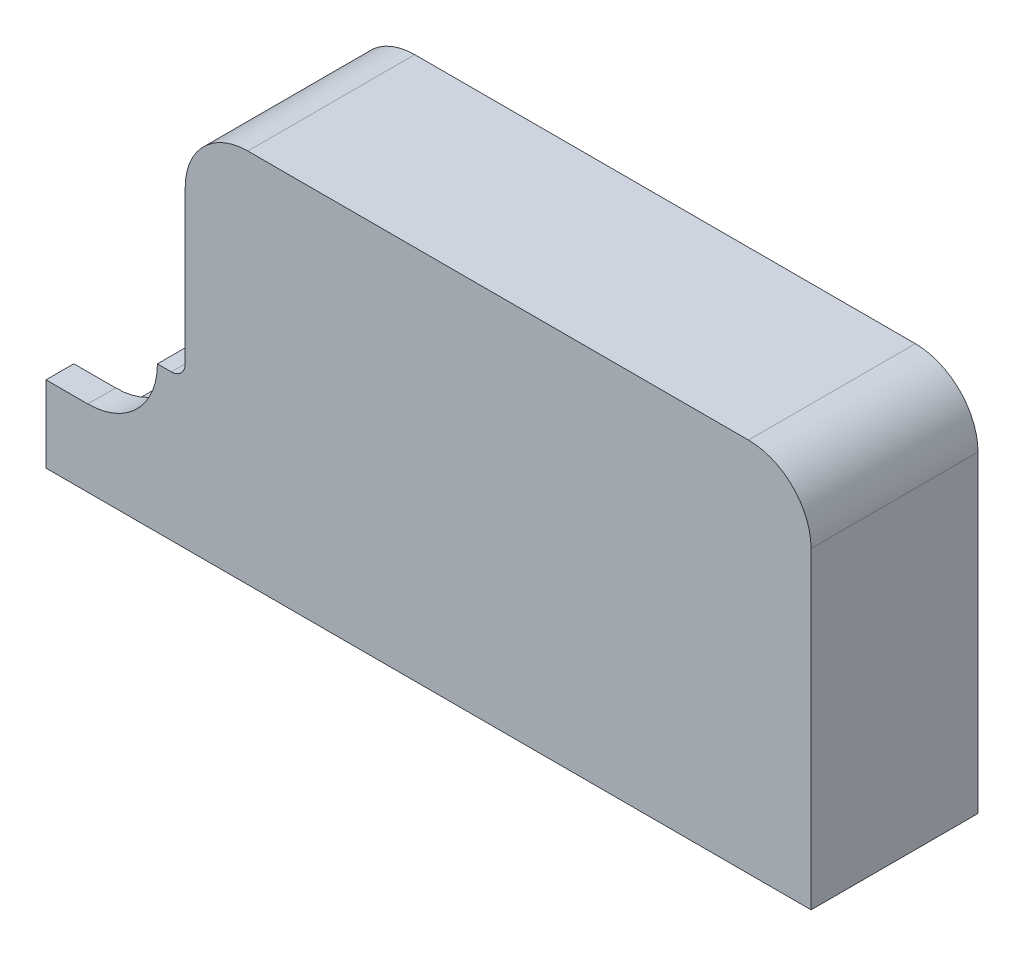
SolidWorks part; units mm, degrees
ref_plane "Front Plane" through (0, 0, 0) normal (0, 0, 1) x (1, 0, 0)
ref_plane "Top Plane" through (0, 0, 0) normal (0, 1, 0) x (1, 0, 0)
ref_plane "Right Plane" through (0, 0, 0) normal (1, 0, 0) x (0, 0, -1)
sketch "Sketch1" plane through (0, 0, 0) normal (0, 0, 1) x (1, 0, 0)
  line L30 (11.5095, 13.5276) -> (11.5095, 22.5276)
  line L31 (15.0095, 26.0276) -> (51, 26.0276)
  line L32 (54.5, 22.5276) -> (54.5, 1.0276)
  line L33 (54.5, 1.0276) -> (1.5, 1.0276)
  line L35 (0.5, 0.0276) -> (0.5, 5.5276)
  line L36 (55.5, 0.0276) -> (0.5, 0.0276)
  line L37 (55.5, 22.5276) -> (55.5, 0.0276)
  line L38 (15.0095, 27.0276) -> (51, 27.0276)
  line L39 (10.5095, 11.5276) -> (10.5095, 22.5276)
  line L40 (0.5, 0.0276) -> (0.5, 1.0276)
  line L41 (55.5, 0.0276) -> (0.5, 0.0276)
  line L42 (55.5, 22.5276) -> (55.5, 0.0276)
  line L43 (15.0095, 27.0276) -> (51, 27.0276)
  line L44 (10.5095, 13.5276) -> (10.5095, 22.5276)
  line L46 (10.5095, 13.5276) -> (11.5095, 13.5276)
  line L47 (8.5095, 11.5276) -> (10.0095, 11.5276) construction
  line L48 (10.5095, 11.5276) -> (10.5095, 22.5276) construction
  line L49 (11.5095, 11.5276) -> (11.5095, 22.5276) construction
  line L50 (1.5, 1.0276) -> (0.5, 1.0276)
  line L52 (0.5, 0.0276) -> (0.5, 5.5276) construction
  line L55 (1.5, 1.0276) -> (1.5, 5.5276) construction
  arc A13 (15.0095, 26.0276) -> (11.5095, 22.5276) centre (15.0095, 22.5276) ccw
  arc A14 (54.5, 22.5276) -> (51, 26.0276) centre (51, 22.5276) ccw
  arc A15 (55.5, 22.5276) -> (51, 27.0276) centre (51, 22.5276) ccw
  arc A16 (15.0095, 27.0276) -> (10.5095, 22.5276) centre (15.0095, 22.5276) ccw
  arc A17 (55.5, 22.5276) -> (51, 27.0276) centre (51, 22.5276) ccw
  arc A18 (15.0095, 27.0276) -> (10.5095, 22.5276) centre (15.0095, 22.5276) ccw
  dimension "D3" = 2
  dimension "D1" = 0.5
  dimension "D2" = 1
extrude "Boss-Extrude1" add sketch "Sketch1" along normal up to surface (12 mm away) from offset 1
sketch "Sketch2" plane through (0, 0, 13) normal (0, 0, 1) x (1, 0, 0)
  line L0 (0.5, 5.5276) -> (8.5095, 5.5276)
  line L1 (8.5095, 5.5276) -> (8.5095, 10.5276)
  line L2 (8.5095, 5.5276) -> (8.5095, 11.5276) construction
  line L3 (8.5095, 10.5276) -> (10.5095, 10.5276)
  line L4 (10.5095, 10.5276) -> (10.5095, 13.5276)
  line L5 (8.5095, 11.5276) -> (10.0095, 11.5276) construction
  line L6 (10.5095, 22.5276) -> (10.5095, 13.5276) construction
  line L7 (0.5, 1.0276) -> (0.5, 5.5276)
  line L8 (0, 5.5276) -> (3.5095, 5.5276) construction
  line L19 (11.5095, 13.5276) -> (11.5095, 22.5276)
  line L20 (15.0095, 26.0276) -> (51, 26.0276)
  line L21 (54.5, 22.5276) -> (54.5, 1.0276)
  line L22 (54.5, 1.0276) -> (0.5, 1.0276)
  line L25 (0.5, 1.0276) -> (0.5, 0.0276)
  line L26 (0.5, 0.0276) -> (55.5, 0.0276)
  line L27 (55.5, 0.0276) -> (55.5, 22.5276)
  line L28 (51, 27.0276) -> (15.0095, 27.0276)
  line L29 (10.5095, 22.5276) -> (10.5095, 13.5276)
  line L30 (10.5095, 13.5276) -> (11.5095, 13.5276)
  line L37 (0.5, 1.0276) -> (0.5, 0.0276)
  line L38 (0.5, 0.0276) -> (55.5, 0.0276)
  line L39 (55.5, 0.0276) -> (55.5, 22.5276)
  line L40 (51, 27.0276) -> (15.0095, 27.0276)
  line L41 (10.5095, 22.5276) -> (10.5095, 13.5276)
  arc A4 (15.0095, 26.0276) -> (11.5095, 22.5276) centre (15.0095, 22.5276) ccw
  arc A5 (54.5, 22.5276) -> (51, 26.0276) centre (51, 22.5276) ccw
  arc A6 (55.5, 22.5276) -> (51, 27.0276) centre (51, 22.5276) ccw
  arc A7 (15.0095, 27.0276) -> (10.5095, 22.5276) centre (15.0095, 22.5276) ccw
  arc A10 (55.5, 22.5276) -> (51, 27.0276) centre (51, 22.5276) ccw
  arc A11 (15.0095, 27.0276) -> (10.5095, 22.5276) centre (15.0095, 22.5276) ccw
  point P0 (7.9922, 5.5276)
  dimension "D1" = 1
  dimension "D2" = 0
extrude "Boss-Extrude2" add sketch "Sketch2" against normal blind 2
sketch "Sketch3" plane through (0, 0, 13) normal (0, 0, 1) x (1, 0, 0)
  circle A0 centre (29.6764, 8.283) radius 2 construction
  circle A1 centre (29.6764, 8.283) radius 2
extrude "Cut-Extrude1" [suppressed] cut sketch "Sketch3" against normal up to next
fillet "Fillet1" radius 5 1 edges at (8.5095, 5.5276, 12)
fillet "Fillet2" radius 1 1 edges at (10.5095, 10.5276, 12)
fillet "Fillet3" radius 1 6 edges at (11.5095, 18.0276, 11) (12.5346, 25.0024, 11) (54.5, 11.7776, 11) (53.4749, 25.0024, 11) (27.5, 1.0276, 11) (33.0047, 26.0276, 11)
